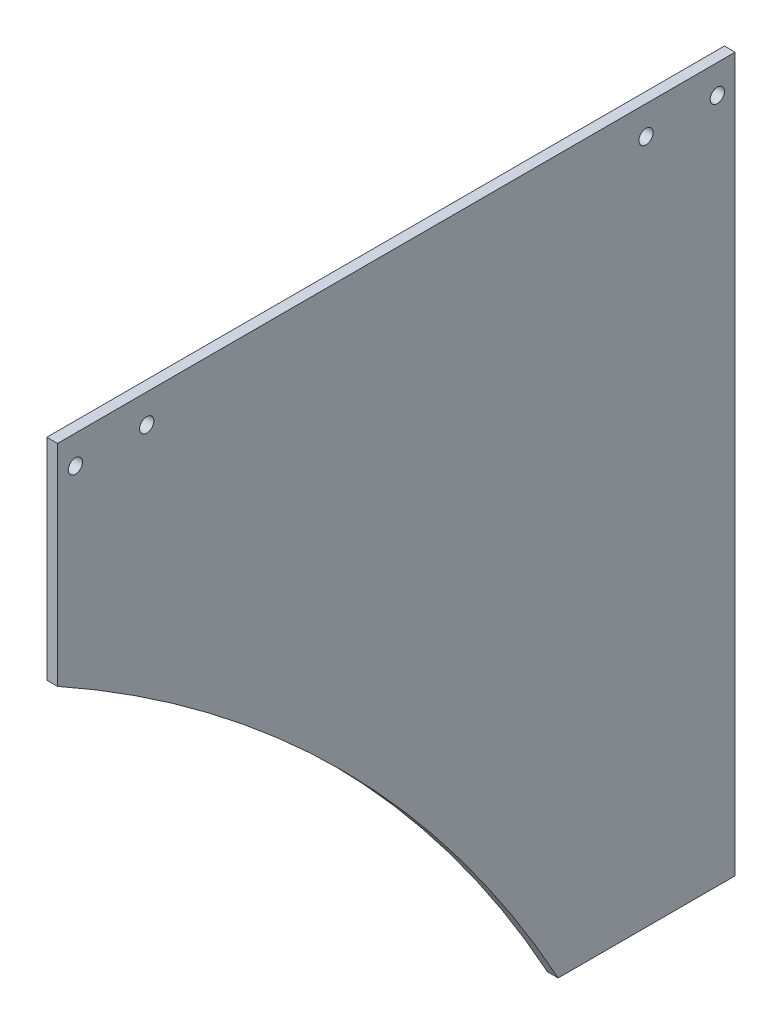
SolidWorks part; units mm, degrees
ref_plane "Спереди" through (0, 0, 0) normal (0, 0, 1) x (1, 0, 0)
ref_plane "Сверху" through (0, 0, 0) normal (0, 1, 0) x (1, 0, 0)
ref_plane "Справа" through (0, 0, 0) normal (1, 0, 0) x (0, 0, -1)
sketch "Эскиз1" plane through (0, 0, 0) normal (1, 0, 0) x (0, 0, -1)
  line L0 (-185, 192) -> (-165, 192) construction
  line L1 (-49.624, 0) -> (0, 0)
  line L2 (-190, 141) -> (-190, 200)
  line L3 (-190, 200) -> (0, 200)
  line L4 (0, 0) -> (0, 200)
  line L5 (-165, 192) -> (-25, 192) construction
  line L6 (-25, 192) -> (-5, 192) construction
  arc A0 (-49.624, 0) -> (-190, 141) centre (-365, -173.6029) ccw
  circle A1 centre (-185, 192) radius 2
  circle A2 centre (-165, 192) radius 2
  circle A3 centre (-25, 192) radius 2
  circle A4 centre (-5, 192) radius 2
  dimension "D3" = 720
  dimension "D7" = 5
  dimension "D10" = 20
  dimension "D11" = 4
  dimension "D1" = 190
  dimension "D2" = 200
  dimension "D4" = 365
  dimension "D5" = 141
  dimension "D6" = 8
  dimension "D8" = 5
  dimension "D9" = 20
base flange "Базовая кромка1" sketch "Эскиз1" thickness 3 reverse thickness direction no parameters "D1"=0.7366
sketch "Сгиб-Линии1" plane through (0, 0, 0) normal (0, 1, 0) x (1, 0, 0)
sketch "Граничная рамка1" plane through (0, 0, 0) normal (0, 1, 0) x (1, 0, 0)
sheet metal parameters "Листовой металл3" thickness 3 parameters "D1"=0.7366
flat pattern "Развертка3" [suppressed]
sketch "Сгиб-Линии2" plane through (0, 0, 0) normal (0, 1, 0) x (1, 0, 0)
sketch "Граничная рамка2" [suppressed] plane through (0, 0, 0) normal (0, 1, 0) x (1, 0, 0)
